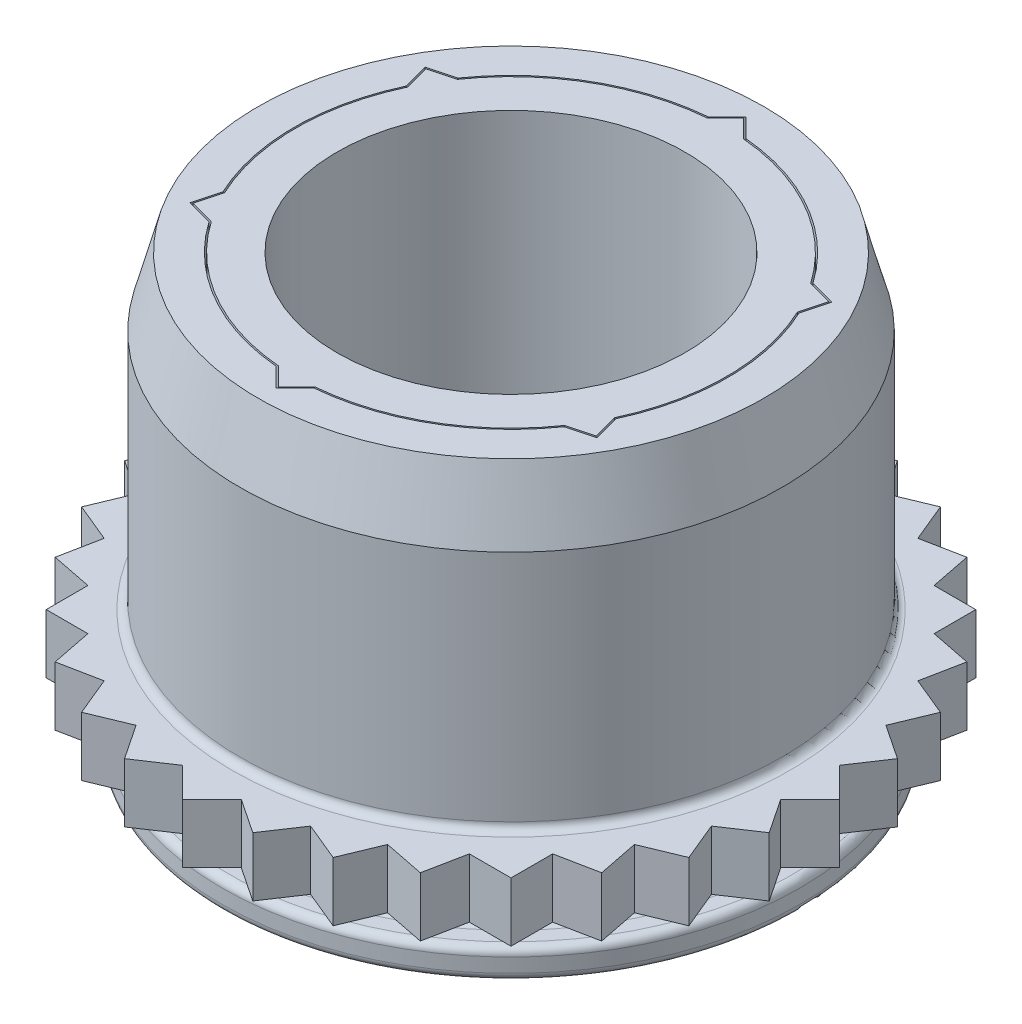
SolidWorks part; units mm, degrees
ref_plane "Front Plane" through (0, 0, 0) normal (0, 0, 1) x (1, 0, 0)
ref_plane "Top Plane" through (0, 0, 0) normal (0, 1, 0) x (1, 0, 0)
ref_plane "Right Plane" through (0, 0, 0) normal (1, 0, 0) x (0, 0, -1)
sketch "Sketch1" plane through (0, 0, 0) normal (1, 0, 0) x (0, 0, -1)
  line L0 (-3.74, 0) -> (3.74, 0) construction
  line L1 (0, 0) -> (0, 5.53) construction
  line L2 (-4.25, 1.1475) -> (4.25, 1.1475) construction
  line L3 (4.25, 1.53) -> (4.25, 0.765) construction
  line L4 (-3.505, 5.53) -> (3.505, 5.53) construction
  line L5 (3.74, 0) -> (3.74, 0.3825) construction
  line L6 (3.74, 0.3825) -> (3.3575, 0.3825) construction
  line L7 (3.3575, 0.3825) -> (3.3575, 0.765) construction
  line L8 (3.3575, 0.765) -> (4.25, 0.765) construction
  line L9 (3.505, 5.53) -> (3.505, 4.65) construction
  line L10 (1.9621, 0.0219) -> (1.9621, -0.6781) construction
  line L11 (1.9621, -0.6781) -> (2.5683, -0.3281) construction
  line L12 (2.5683, -0.3281) -> (2.4926, -0.3281) construction
  line L13 (1.9621, 0.0219) -> (2.5683, -0.3281) construction
  line L14 (2.0379, -0.0219) -> (2.0379, -0.6344) construction
  line L15 (2.4926, -0.2844) -> (2.4926, -0.3719) construction
  line L16 (2.0379, -0.3281) -> (1.9621, -0.3281) construction
  line L17 (2, 0) -> (2, -0.6562) construction
  point P4 (0, 0)
  point P10 (0, 1.1475)
  point P13 (4.25, 1.1475)
  point P15 (0, 5.53)
  point P16 (-2.804, 5.53)
  point P20 (2.804, 5.53)
  point P21 (-2, 0)
  point P22 (0, 2.33)
  point P23 (2, 0)
  point P31 (2.0379, -0.3281)
  point P34 (2.4926, -0.3281)
  point P39 (2, -0.3281)
  point P40 (2.25, 5.53)
  point P41 (-2.25, 5.53)
  dimension "D1" = 0.765
  dimension "D2" = 0.3825
  dimension "D3" = 3.2
  dimension "D4" = 0.88
  dimension "D5" = 60
  dimension "D6" = 0.7
  dimension "D7" = 0.0875
sketch "Sketch2" plane through (0, 0, 0) normal (1, 0, 0) x (0, 0, -1)
  line L0 (2.804, 5.53) -> (3.2692, 5.53)
  line L1 (3.505, 4.65) -> (3.505, 1.63)
  line L2 (3.605, 1.53) -> (4.25, 1.53)
  line L3 (4.25, 1.53) -> (4.25, 0.765)
  line L4 (4.25, 0.765) -> (3.4575, 0.765)
  line L5 (3.3575, 0.665) -> (3.3575, 0.4825)
  line L6 (3.4575, 0.3825) -> (3.64, 0.3825)
  line L7 (3.74, 0.2825) -> (3.74, 0.1)
  line L8 (3.64, 0) -> (2.433, 0)
  line L10 (2, 0.433) -> (2, 1.897)
  line L12 (2.804, 2.33) -> (2.804, 5.53)
  line L14 (3.2692, 5.53) -> (3.505, 4.65)
  line L15 (2.804, 2.33) -> (2.433, 2.33)
  line L16 (2.433, 2.33) -> (2, 1.897)
  line L17 (2, 0.433) -> (2.433, 0)
  line L18 (-3.74, 0) -> (3.74, 0) construction
  line L19 (-4.25, 1.1475) -> (4.25, 1.1475) construction
  arc A1 (3.64, 0) -> (3.74, 0.1) centre (3.64, 0.1) ccw
  arc A2 (3.74, 0.2825) -> (3.64, 0.3825) centre (3.64, 0.2825) ccw
  arc A3 (3.605, 1.53) -> (3.505, 1.63) centre (3.605, 1.63) cw
  arc A4 (3.4575, 0.765) -> (3.3575, 0.665) centre (3.4575, 0.665) ccw
  arc A5 (3.3575, 0.4825) -> (3.4575, 0.3825) centre (3.4575, 0.4825) ccw
  point P32 (3.74, 0)
  point P36 (3.74, 0.3825)
  point P41 (3.3575, 0.765)
  point P44 (3.3575, 0.3825)
  dimension "D1" = 0.1
  dimension "D3" = 0.1
  dimension "D2" = 15
  dimension "D4" = 45
  dimension "D5" = 0.433
revolve "Body Revolve" add sketch "Sketch2" angle 360 about L1
sketch "Sketch5" plane through (0, 1.53, 0) normal (0, 1, 0) x (1, 0, 0)
  line L0 (4.25, 0) -> (-4.25, 0) construction
  line L2 (0, 0) -> (0, -4.25) construction
  line L4 (0, -4.25) -> (0, 4.25) construction
  line L5 (-4.25, 0) -> (-3.8689, -0.3811)
  line L6 (-4.25, 0) -> (-3.8689, 0.3811)
  line L7 (-4.1683, 0.8291) -> (-3.7203, 1.1285)
  line L8 (-4.1683, 0.8291) -> (-3.8689, 0.3811)
  line L9 (-3.9265, 1.6264) -> (-3.4286, 1.8326)
  line L10 (-3.9265, 1.6264) -> (-3.7203, 1.1285)
  line L11 (-3.5337, 2.3612) -> (-3.0052, 2.4663)
  line L12 (-3.5337, 2.3612) -> (-3.4286, 1.8326)
  line L13 (-3.0052, 3.0052) -> (-2.4663, 3.0052)
  line L14 (-3.0052, 3.0052) -> (-3.0052, 2.4663)
  line L15 (-2.3612, 3.5337) -> (-1.8326, 3.4286)
  line L16 (-2.3612, 3.5337) -> (-2.4663, 3.0052)
  line L17 (-1.6264, 3.9265) -> (-1.1285, 3.7203)
  line L18 (-1.6264, 3.9265) -> (-1.8326, 3.4286)
  line L19 (-0.8291, 4.1683) -> (-0.3811, 3.8689)
  line L20 (-0.8291, 4.1683) -> (-1.1285, 3.7203)
  line L21 (0, 4.25) -> (0.3811, 3.8689)
  line L22 (0, 4.25) -> (-0.3811, 3.8689)
  line L23 (0.8291, 4.1683) -> (1.1285, 3.7203)
  line L24 (0.8291, 4.1683) -> (0.3811, 3.8689)
  line L25 (1.6264, 3.9265) -> (1.8326, 3.4286)
  line L26 (1.6264, 3.9265) -> (1.1285, 3.7203)
  line L27 (2.3612, 3.5337) -> (2.4663, 3.0052)
  line L28 (2.3612, 3.5337) -> (1.8326, 3.4286)
  line L29 (3.0052, 3.0052) -> (3.0052, 2.4663)
  line L30 (3.0052, 3.0052) -> (2.4663, 3.0052)
  line L31 (3.5337, 2.3612) -> (3.4286, 1.8326)
  line L32 (3.5337, 2.3612) -> (3.0052, 2.4663)
  line L33 (3.9265, 1.6264) -> (3.7203, 1.1285)
  line L34 (3.9265, 1.6264) -> (3.4286, 1.8326)
  line L35 (4.1683, 0.8291) -> (3.8689, 0.3811)
  line L36 (4.1683, 0.8291) -> (3.7203, 1.1285)
  line L37 (4.25, 0) -> (3.8689, -0.3811)
  line L38 (4.25, 0) -> (3.8689, 0.3811)
  line L39 (4.1683, -0.8291) -> (3.7203, -1.1285)
  line L40 (4.1683, -0.8291) -> (3.8689, -0.3811)
  line L41 (3.9265, -1.6264) -> (3.4286, -1.8326)
  line L42 (3.9265, -1.6264) -> (3.7203, -1.1285)
  line L43 (3.5337, -2.3612) -> (3.0052, -2.4663)
  line L44 (3.5337, -2.3612) -> (3.4286, -1.8326)
  line L45 (3.0052, -3.0052) -> (2.4663, -3.0052)
  line L46 (3.0052, -3.0052) -> (3.0052, -2.4663)
  line L47 (2.3612, -3.5337) -> (1.8326, -3.4286)
  line L48 (2.3612, -3.5337) -> (2.4663, -3.0052)
  line L49 (1.6264, -3.9265) -> (1.1285, -3.7203)
  line L50 (1.6264, -3.9265) -> (1.8326, -3.4286)
  line L51 (0.8291, -4.1683) -> (0.3811, -3.8689)
  line L52 (0.8291, -4.1683) -> (1.1285, -3.7203)
  line L53 (0, -4.25) -> (-0.3811, -3.8689)
  line L54 (0, -4.25) -> (0.3811, -3.8689)
  line L55 (-0.8291, -4.1683) -> (-1.1285, -3.7203)
  line L56 (-0.8291, -4.1683) -> (-0.3811, -3.8689)
  line L57 (-1.6264, -3.9265) -> (-1.8326, -3.4286)
  line L58 (-1.6264, -3.9265) -> (-1.1285, -3.7203)
  line L59 (-2.3612, -3.5337) -> (-2.4663, -3.0052)
  line L60 (-2.3612, -3.5337) -> (-1.8326, -3.4286)
  line L61 (-3.0052, -3.0052) -> (-3.0052, -2.4663)
  line L62 (-3.0052, -3.0052) -> (-2.4663, -3.0052)
  line L63 (-3.5337, -2.3612) -> (-3.4286, -1.8326)
  line L64 (-3.5337, -2.3612) -> (-3.0052, -2.4663)
  line L65 (-3.9265, -1.6264) -> (-3.7203, -1.1285)
  line L66 (-3.9265, -1.6264) -> (-3.4286, -1.8326)
  line L67 (-4.1683, -0.8291) -> (-3.8689, -0.3811)
  line L68 (-4.1683, -0.8291) -> (-3.7203, -1.1285)
  circle A0 centre (0, 0) radius 4.25 construction
  circle A2 centre (0, 0) radius 4.25 construction
  point P3 (0, 0)
  point P10 (0, -2.125)
  point P111 (0, 0)
  dimension "D2" = 32
extrude "Cut-Extrude3" cut sketch "Sketch5" against normal through all both and the other way through all flip side to cut
sketch "Sketch3" plane through (0, 5.53, 0) normal (0, 1, 0) x (1, 0, 0)
  line L0 (2.804, 0) -> (-2.804, 0) construction
  line L1 (0, 2.804) -> (0, 3.505) construction
  line L2 (-0.2443, 2.7933) -> (0, 3.0377)
  line L4 (0, -3.74) -> (0, 3.74) construction
  line L5 (0, 3.0377) -> (0.2443, 2.7933)
  line L8 (2.2969, 1.6083) -> (2.6307, 1.5188)
  line L9 (0, 2.804) -> (0, 3.0377) construction
  line L10 (2.6307, 1.5188) -> (2.5413, 1.1851)
  line L11 (2.5413, -1.1851) -> (2.6307, -1.5188)
  line L12 (2.6307, -1.5188) -> (2.2969, -1.6083)
  line L13 (0.2443, -2.7933) -> (0, -3.0377)
  line L14 (0, -3.0377) -> (-0.2443, -2.7933)
  line L15 (-2.2969, -1.6083) -> (-2.6307, -1.5188)
  line L16 (-2.6307, -1.5188) -> (-2.5413, -1.1851)
  line L17 (-2.5413, 1.1851) -> (-2.6307, 1.5188)
  line L18 (-2.6307, 1.5188) -> (-2.2969, 1.6083)
  arc A1 (-2.2969, -1.6083) -> (-0.2443, -2.7933) centre (0, 0) ccw
  circle A3 centre (0, 0) radius 2.804 construction
  arc A5 (-0.2443, 2.7933) -> (-2.2969, 1.6083) centre (0, 0) ccw
  arc A6 (0.2443, -2.7933) -> (2.2969, -1.6083) centre (0, 0) ccw
  circle A7 centre (0, 0) radius 3.505
  circle A8 centre (0, 0) radius 3.505 construction
  arc A9 (2.5413, -1.1851) -> (2.5413, 1.1851) centre (0, 0) ccw
  arc A10 (2.2969, 1.6083) -> (0.2443, 2.7933) centre (0, 0) ccw
  arc A11 (-2.5413, 1.1851) -> (-2.5413, -1.1851) centre (0, 0) ccw
  point P32 (0, 0)
  dimension "D2" = 0.2337
  dimension "D4" = 0.701
extrude "Insert Hole Cut" cut sketch "Sketch3" against normal up to surface (3.2 mm away) contours L2 L5 A10 L8 L10 A9 L11 L12 A6 L13 L14 A1 L15 L16 A11 L17 L18 A5 up to face at (0, 2.33, -2.433)
sketch "Sketch4" plane through (0, 5.53, 0) normal (0, 1, 0) x (1, 0, 0)
  line L0 (2.6062, -1.5047) -> (2.5201, -1.1832)
  line L1 (2.5201, 1.1832) -> (2.6062, 1.5047)
  line L2 (2.6062, 1.5047) -> (2.2847, 1.5908)
  line L3 (0.2353, 2.774) -> (0, 3.0094)
  line L4 (0, 3.0094) -> (-0.2353, 2.774)
  line L5 (-2.2847, 1.5908) -> (-2.6062, 1.5047)
  line L6 (-2.6062, 1.5047) -> (-2.5201, 1.1832)
  line L7 (-2.5201, -1.1832) -> (-2.6062, -1.5047)
  line L8 (-2.6062, -1.5047) -> (-2.2847, -1.5908)
  line L9 (-0.2353, -2.774) -> (0, -3.0094)
  line L10 (0, -3.0094) -> (0.2353, -2.774)
  line L11 (2.2847, -1.5908) -> (2.6062, -1.5047)
  line L12 (2.6307, -1.5188) -> (2.5413, -1.1851)
  line L13 (2.2969, -1.6083) -> (2.6307, -1.5188)
  line L14 (0, -3.0377) -> (0.2443, -2.7933)
  line L15 (-0.2443, -2.7933) -> (0, -3.0377)
  line L16 (-2.6307, -1.5188) -> (-2.2969, -1.6083)
  line L17 (-2.5413, -1.1851) -> (-2.6307, -1.5188)
  line L18 (-2.6307, 1.5188) -> (-2.5413, 1.1851)
  line L19 (-2.2969, 1.6083) -> (-2.6307, 1.5188)
  line L20 (0, 3.0377) -> (-0.2443, 2.7933)
  line L21 (0.2443, 2.7933) -> (0, 3.0377)
  line L22 (2.6307, 1.5188) -> (2.2969, 1.6083)
  line L23 (2.5413, 1.1851) -> (2.6307, 1.5188)
  line L24 (2.6307, -1.5188) -> (2.5413, -1.1851) construction
  line L25 (2.2969, -1.6083) -> (2.6307, -1.5188) construction
  line L26 (0, -3.0377) -> (0.2443, -2.7933) construction
  line L27 (-0.2443, -2.7933) -> (0, -3.0377) construction
  line L28 (-2.6307, -1.5188) -> (-2.2969, -1.6083) construction
  line L29 (-2.5413, -1.1851) -> (-2.6307, -1.5188) construction
  line L30 (-2.6307, 1.5188) -> (-2.5413, 1.1851) construction
  line L31 (-2.2969, 1.6083) -> (-2.6307, 1.5188) construction
  line L32 (0, 3.0377) -> (-0.2443, 2.7933) construction
  line L33 (0.2443, 2.7933) -> (0, 3.0377) construction
  line L34 (2.6307, 1.5188) -> (2.2969, 1.6083) construction
  line L35 (2.5413, 1.1851) -> (2.6307, 1.5188) construction
  arc A0 (2.5201, -1.1832) -> (2.5201, 1.1832) centre (0, 0) ccw
  arc A1 (2.2847, 1.5908) -> (0.2353, 2.774) centre (0, 0) ccw
  arc A2 (-0.2353, 2.774) -> (-2.2847, 1.5908) centre (0, 0) ccw
  arc A3 (-2.5201, 1.1832) -> (-2.5201, -1.1832) centre (0, 0) ccw
  arc A4 (-2.2847, -1.5908) -> (-0.2353, -2.774) centre (0, 0) ccw
  arc A5 (0.2353, -2.774) -> (2.2847, -1.5908) centre (0, 0) ccw
  arc A6 (0.2443, -2.7933) -> (2.2969, -1.6083) centre (0, 0) ccw
  arc A7 (-2.2969, -1.6083) -> (-0.2443, -2.7933) centre (0, 0) ccw
  arc A8 (-2.5413, 1.1851) -> (-2.5413, -1.1851) centre (0, 0) ccw
  arc A9 (-0.2443, 2.7933) -> (-2.2969, 1.6083) centre (0, 0) ccw
  arc A10 (2.2969, 1.6083) -> (0.2443, 2.7933) centre (0, 0) ccw
  arc A11 (2.5413, -1.1851) -> (2.5413, 1.1851) centre (0, 0) ccw
  arc A12 (0.2443, -2.7933) -> (2.2969, -1.6083) centre (0, 0) ccw construction
  arc A13 (-2.2969, -1.6083) -> (-0.2443, -2.7933) centre (0, 0) ccw construction
  arc A14 (-2.5413, 1.1851) -> (-2.5413, -1.1851) centre (0, 0) ccw construction
  arc A15 (-0.2443, 2.7933) -> (-2.2969, 1.6083) centre (0, 0) ccw construction
  arc A16 (2.2969, 1.6083) -> (0.2443, 2.7933) centre (0, 0) ccw construction
  arc A17 (2.5413, -1.1851) -> (2.5413, 1.1851) centre (0, 0) ccw construction
  circle A18 centre (0, 0) radius 2.25
  dimension "D1" = 0
  dimension "D2" = 0.02
extrude "Insert Extrude" add sketch "Sketch4" against normal up to surface (3.2 mm away) separate body up to face at (0, 2.33, -2.433)
sketch "Sketch8" plane through (0, 0, 0) normal (0, 1, 0) x (1, 0, 0)
  circle A0 centre (0, 0) radius 2 construction
  circle A1 centre (0, 0) radius 4.25 construction
sketch "Sketch6" [suppressed] plane through (0, 0, 0) normal (0, -1, 0) x (1, 0, 0)
  circle A0 centre (0, 0) radius 2 construction
  circle A1 centre (0, 0) radius 2
curve "Helix/Spiral1" [suppressed] pitch 0.7 height 5.53 turns 7.9 parameters "Pitch"=0.7
sketch "Sketch7" [suppressed] plane through (0, 0, 0) normal (1, 0, 0) x (0, 0, -1)
  line L0 (2, 0) -> (2, -0.6562)
  line L1 (2, -0.6562) -> (2.4926, -0.3719)
  line L2 (2.4926, -0.3719) -> (2.4926, -0.2844)
  line L3 (2.4926, -0.2844) -> (2, 0)
sweep "Cut-Sweep1" [suppressed] cut profiles "Sketch7" path "Helix/Spiral1"
ref_axis "Center Axis 1" through (0, 0, 0) along (0, 1, 0)
ref_plane "Contact Plane 1" through (0, 0, 0) normal (0, -1, 0) x (-1, 0, 0)
equation "\"D1@Sketch1\"=\"Shank (A)@Sketch1\"/2"
equation "\"D2@Sketch1\"=\"D1@Sketch1\"/2"
equation "\"Insert @Sketch1\"=\"D@Sketch1\"*.8"
equation "\"D3@Sketch1\"=\"Head Height (T)@Sketch1\"*.8"
equation "\"D4@Sketch1\"=\"Head Height (T)@Sketch1\"*.22"
equation "\"D3@Sketch2\"=\"D1@Sketch2\""
equation "\"D2@Sketch3\"=\"D4@Sketch3\"/3"
equation "\"D6@Sketch1\"=\"Pitch@Helix/Spiral1\""
equation "\"D7@Sketch1\"=\"Pitch@Helix/Spiral1\"/8"
equation "\"D3@Helix/Spiral1\"=(\"Head Height (T)@Sketch1\"+\"Shank (A)@Sketch1\")"
